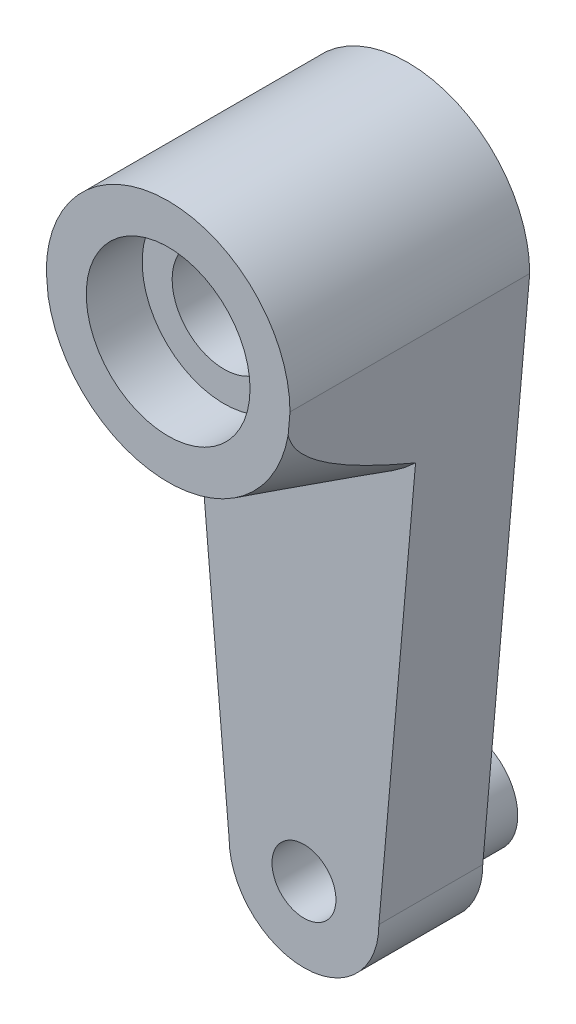
SolidWorks part; units mm, degrees
ref_plane "前视基准面" through (0, 0, 0) normal (0, 0, 1) x (1, 0, 0)
ref_plane "上视基准面" through (0, 0, 0) normal (0, 1, 0) x (1, 0, 0)
ref_plane "右视基准面" through (0, 0, 0) normal (1, 0, 0) x (0, 0, -1)
sketch "草图1" plane through (0, 0, 0) normal (0, 0, 1) x (1, 0, 0)
  line L0 (-3.75, -26.8) -> (-6.1, 0)
  line L1 (6.1, 0) -> (3.75, -26.8)
  arc A0 (6.1, 0) -> (-6.1, 0) centre (0, 0) ccw
  arc A1 (-3.75, -26.8) -> (3.75, -26.8) centre (0, -26.8) ccw
  circle A2 centre (0, 0) radius 2.6
  circle A3 centre (0, -26.8) radius 1.6
extrude "凸台-拉伸1" add sketch "草图1" along normal blind 12
sketch "草图3" plane through (0, 0, 12) normal (0, 0, 1) x (1, 0, 0)
  line L0 (-6.0069, -1.0616) -> (-3.75, -26.8)
  line L1 (3.75, -26.8) -> (6.0069, -1.0616)
  arc A0 (-6.0069, -1.0616) -> (6.0069, -1.0616) centre (0, 0) ccw
  arc A1 (-3.75, -26.8) -> (3.75, -26.8) centre (0, -26.8) ccw
extrude "切除-拉伸1" cut sketch "草图3" against normal blind 6.8
sketch "草图4" plane through (0, 0, 0) normal (0, 0, -1) x (-1, 0, 0)
  circle A0 centre (0, 0) radius 4.1
  dimension "D1" = 8.2
extrude "切除-拉伸2" cut sketch "草图4" against normal blind 2.8
sketch "草图5" plane through (0, 0, 0) normal (0, 0, -1) x (-1, 0, 0)
  circle A0 centre (0, -26.8) radius 2.5
  circle A1 centre (0, -26.8) radius 1.6
  dimension "D1" = 5
extrude "凸台-拉伸2" add sketch "草图5" along normal blind 3
chamfer "倒角1" distance 0.5 distance2 0.5 1 edges at (2.5, -26.8, 0)
sketch "草图6" plane through (0, 0, 12) normal (0, 0, 1) x (1, 0, 0)
  circle A0 centre (0, 0) radius 2.6
  circle A1 centre (0, 0) radius 4.1
  dimension "D1" = 8.2
extrude "切除-拉伸3" cut sketch "草图6" against normal blind 2.8
chamfer "倒角2" distance 6.8 distance2 2 1 edges at (0, -6.1, 5.2) first distance on face at (0, -3.5808, 8.6)
